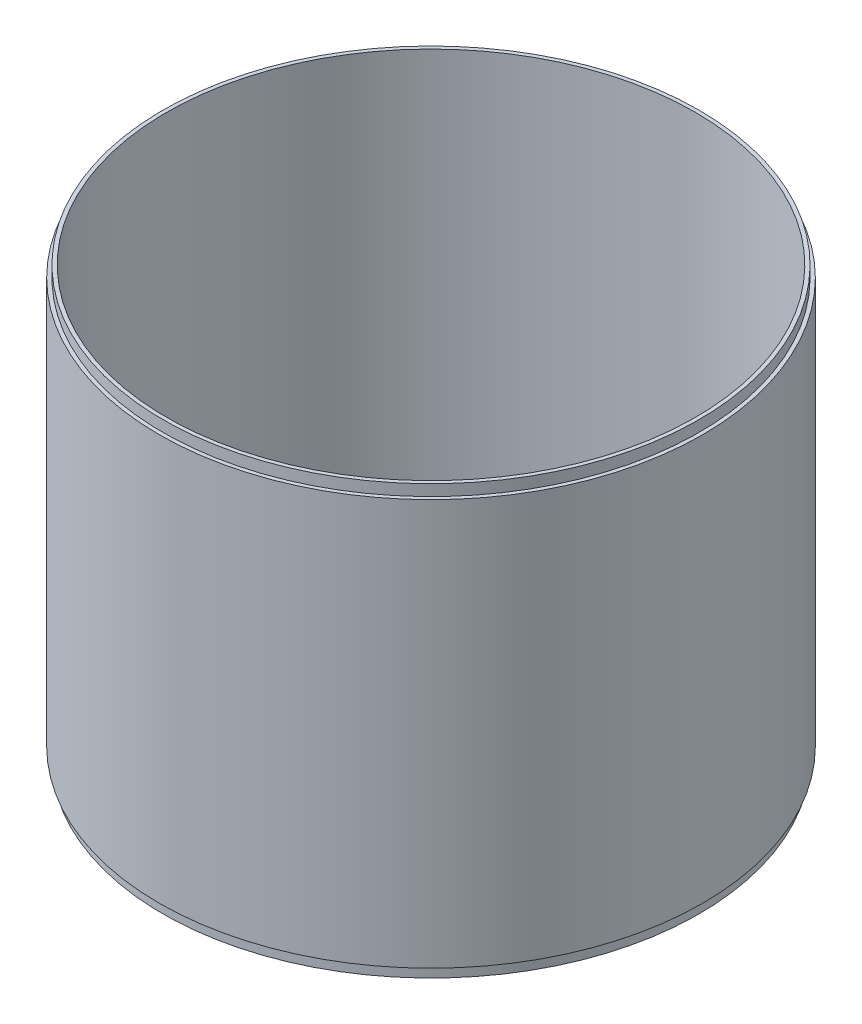
SolidWorks part; units mm, degrees
material "Silica Phenolic"
ref_plane "Piano frontale" through (0, 0, 0) normal (0, 0, 1) x (1, 0, 0)
ref_plane "Piano superiore" through (0, 0, 0) normal (0, 1, 0) x (1, 0, 0)
ref_plane "Piano destro" through (0, 0, 0) normal (1, 0, 0) x (0, 0, -1)
sketch "Schizzo1" plane through (0, 0, 0) normal (0, 0, 1) x (1, 0, 0)
  line L0 (-71, 3) -> (-71, 0)
  line L3 (-72, 115) -> (-71, 115)
  line L8 (0, 0) -> (0, 47.1479) construction
  line L9 (-71, 0) -> (-72, 0)
  line L10 (-72, 0) -> (-72, 3)
  line L11 (-72, 3) -> (-73, 3)
  line L12 (-71, 3) -> (-71, 115)
  line L13 (-73, 3) -> (-73, 112)
  line L14 (-73, 112) -> (-72, 112)
  line L15 (-72, 112) -> (-72, 115)
  point P2 (-72.3311, 113.3384)
  dimension "D1" = 1
  dimension "D2" = 3
  dimension "D3" = 3
  dimension "D4" = 1
  dimension "D5" = 1
  dimension "D6" = 115
  dimension "D7" = 146
revolve "Rivoluzione1" add sketch "Schizzo1" angle 360 about L8 region at (-71.9866, 57.5, 0)
